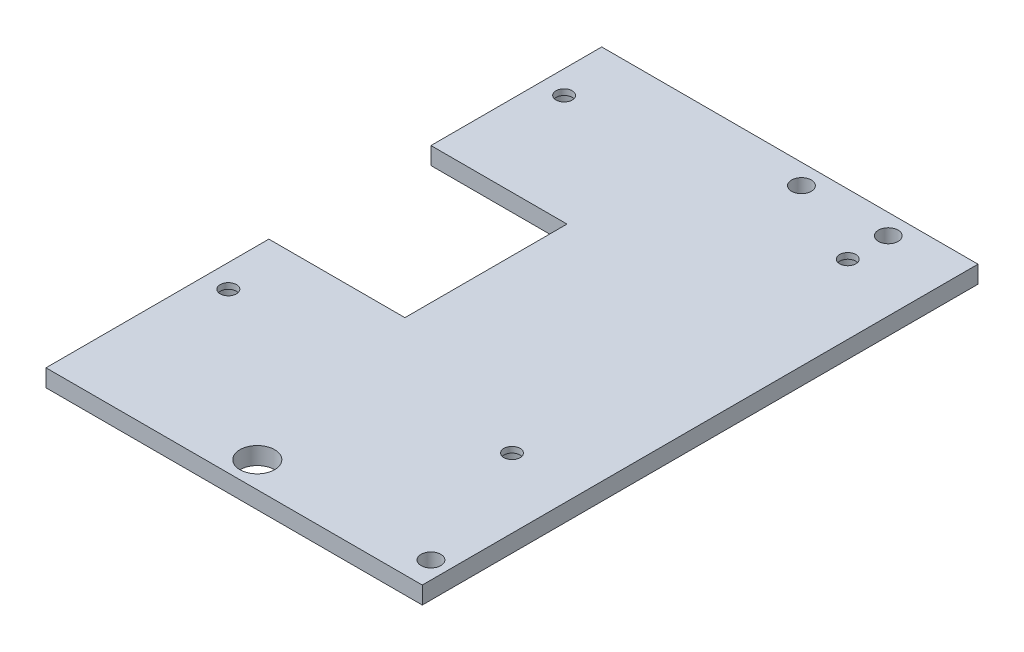
SolidWorks part; units mm, degrees
note: The reader was unsure of these and kept them because the rebuilt part matched: shared geometry of "Esquisse1<3>".
ref_plane "Plan de face" through (0, 0, 0) normal (0, 0, 1) x (1, 0, 0)
ref_plane "Plan de dessus" through (0, 0, 0) normal (0, 1, 0) x (1, 0, 0)
ref_plane "Plan de droite" through (0, 0, 0) normal (1, 0, 0) x (0, 0, -1)
sketch "Esquisse1" plane through (0, 0, 0) normal (0, 1, 0) x (1, 0, 0)
  line L0 (0, 55.5627) -> (0, -56.543) construction
  line L1 (-45.5, 48) -> (19.5, 48)
  line L2 (-45.5, 48) -> (-45.5, -48)
  line L3 (-45.5, -48) -> (19.5, -48)
  line L4 (19.5, 48) -> (19.5, -48)
  line L5 (0, -55) -> (0, 55) construction
  line L6 (-55, 0) -> (55, 0) construction
  line L7 (-22, 18.5) -> (-22, -9.5)
  line L8 (-22, -9.5) -> (-45.5, -9.5)
  line L9 (-45.5, -9.5) -> (-45.5, 18.5)
  line L10 (-45.5, 18.5) -> (-22, 18.5)
  circle A0 centre (-7.5, 44.5) radius 1.7
  circle A1 centre (7.5, 44.5) radius 1.7
  circle A2 centre (-13.5, -43.5) radius 3
  circle A3 centre (16.5, -43.5) radius 1.7
  circle A4 centre (-41.5, 37.5) radius 1.4
  circle A5 centre (7.5, 37.5) radius 1.4
  circle A6 centre (7.5, -20.5) radius 1.4
  circle A7 centre (-41.5, -20.5) radius 1.4
  circle A8 centre (-41.5, -20.5) radius 2.4
  circle A9 centre (7.5, -20.5) radius 2.4
  circle A10 centre (7.5, 37.5) radius 2.4
  circle A11 centre (-41.5, 37.5) radius 2.4
  point P22 (19.5, 0)
  dimension "D4" = 3.4
  dimension "D5" = 3.4
  dimension "D7" = 6
  dimension "D8" = 3.4
  dimension "D16" = 2.8
  dimension "D17" = 2.8
  dimension "D18" = 2.8
  dimension "D19" = 2.8
  dimension "D24" = 4.8
  dimension "D1" = 96
  dimension "D2" = 65
  dimension "D3" = 15
  dimension "D6" = 30
  dimension "D9" = 7.5
  dimension "D10" = 13.5
  dimension "D11" = 88
  dimension "D12" = 12
  dimension "D13" = 3.5
  dimension "D14" = 58
  dimension "D15" = 49
  dimension "D20" = 7
  dimension "D21" = 22
  dimension "D22" = 28
  dimension "D23" = 26
extrude "Boss.-Extru.1" add sketch "Esquisse1" along normal blind 3 contours L0 L1 L2 L10 L7 L8 L3 A7 A4 A2 A0 | L1 L0 L3 L4 A1 A3 A5 A6 | A10 A5 | A11 A4 | A8 A7 | A6 | A9
extrude "Enlèv. mat.-Extru.1" cut sketch "Esquisse1<3>" along normal blind 2 contours A8 A7 | A9 A6 | A10 A5 | A11 A4
sketch "Esquisse1<3>" plane through (0, 0, 0) normal (0, 1, 0) x (1, 0, 0) same geometry as "Esquisse1"
equation "\"D8@Esquisse1\"=\"D4@Esquisse1\""
equation "\"D5@Esquisse1\"=\"D4@Esquisse1\""
equation "\"D17@Esquisse1\"=\"D16@Esquisse1\""
equation "\"D18@Esquisse1\"=\"D16@Esquisse1\""
equation "\"D19@Esquisse1\"=\"D16@Esquisse1\""
